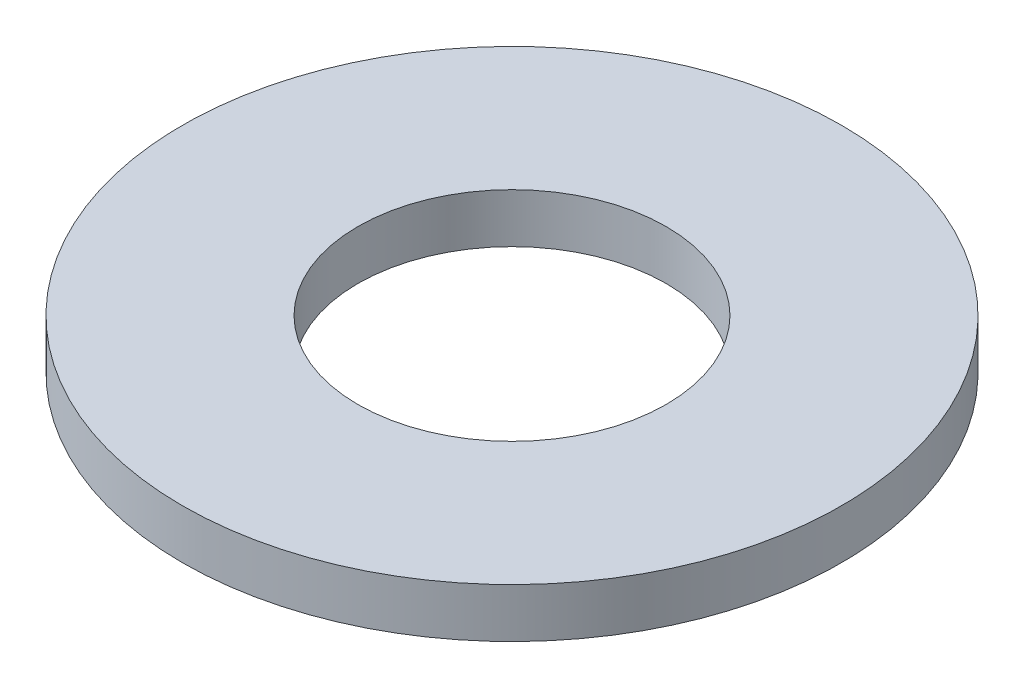
SolidWorks part; units mm, degrees
material "1023 Carbon Steel Sheet (SS)"
ref_plane "Front" through (0, 0, 0) normal (0, 0, 1) x (1, 0, 0)
ref_plane "Top" through (0, 0, 0) normal (0, 1, 0) x (1, 0, 0)
ref_plane "Right" through (0, 0, 0) normal (1, 0, 0) x (0, 0, -1)
ref_axis "side-side" through (80.9, 0, 0) along (-1, 0, 0)
ref_axis "up-down" through (0, 50, 0) along (0, -1, 0)
ref_axis "front-back" through (0, 0, -80.9) along (0, 0, 1)
sketch "Sketch1" plane through (0, 0, 0) normal (0, 1, 0) x (1, 0, 0)
  circle A0 centre (0, 0) radius 2.5781
  circle A1 centre (0, 0) radius 5.5118
  dimension "D1" = 11.0236
  dimension "D2" = 5.1562
extrude "Boss-Extrude1" add sketch "Sketch1" along normal blind 0.8255
